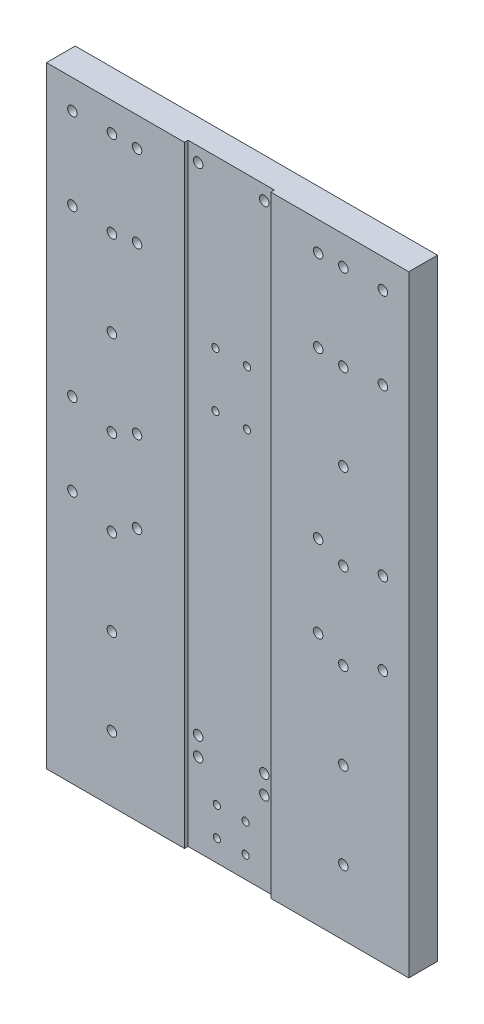
SolidWorks part; units mm, degrees
ref_plane "Piano frontale" through (0, 0, 0) normal (0, 0, 1) x (1, 0, 0)
ref_plane "Piano superiore" through (0, 0, 0) normal (0, 1, 0) x (1, 0, 0)
ref_plane "Piano destro" through (0, 0, 0) normal (1, 0, 0) x (0, 0, -1)
sketch "Schizzo1" plane through (0, 0, 0) normal (0, 0, 1) x (1, 0, 0)
  line L1 (126, -250) -> (-126, -250)
  line L2 (126, -250) -> (126, 250)
  line L3 (126, 250) -> (-126, 250)
  line L4 (-126, -250) -> (-126, 250)
  line L5 (126, -250) -> (-126, 250) construction
  line L6 (126, 250) -> (-126, -250) construction
  point P0 (0, 0)
  dimension "D1" = 252
  dimension "D2" = 500
extrude "Estrusione-Estrusione1" add sketch "Schizzo1" along normal blind 20
sketch "Schizzo2" plane through (0, 0, 20) normal (0, 0, 1) x (1, 0, 0)
  line L0 (1265.2426, 21.4119) -> (-695.7574, 21.4119) construction
  line L1 (1265.2426, 13.5541) -> (-695.7574, 13.5541) construction
  line L2 (1265.2426, 53.5541) -> (-695.7574, 53.5541) construction
  line L3 (1265.2426, 61.4119) -> (-695.7574, 61.4119) construction
  line L4 (-126, 250) -> (-126, -250)
  line L5 (-126, -250) -> (126, -250)
  line L6 (126, -250) -> (126, 250)
  line L7 (126, 250) -> (-126, 250)
  line L8 (-126, 250) -> (-126, -250) construction
  line L9 (-126, -250) -> (126, -250) construction
  line L10 (126, -250) -> (126, 250) construction
  line L11 (126, 250) -> (-126, 250) construction
  line L12 (1265.2426, 21.4119) -> (-695.7574, 21.4119) construction
  line L13 (1265.2426, 13.5541) -> (-695.7574, 13.5541) construction
  line L14 (1265.2426, 53.5541) -> (-695.7574, 53.5541) construction
  line L15 (1265.2426, 61.4119) -> (-695.7574, 61.4119) construction
  line L16 (126, -45.017) -> (-126, -45.017) construction
  line L17 (126, -25.017) -> (-126, -25.017) construction
  line L18 (126, -45.017) -> (-126, -45.017) construction
  line L19 (126, -25.017) -> (-126, -25.017) construction
  line L20 (-126, -45.017) -> (-126, -25.017) construction
  line L21 (126, -35.017) -> (-126, -35.017) construction
  line L22 (-126, -45.017) -> (126, -45.017) construction
  line L23 (-126, -45.017) -> (-126, -25.017) construction
  line L24 (-126, -25.017) -> (126, -25.017) construction
  line L25 (126, -45.017) -> (126, -25.017) construction
  circle A0 centre (110, 17.483) radius 3.9289
  circle A1 centre (110, 57.483) radius 3.9289
  circle A2 centre (-110, 17.483) radius 3.9289
  circle A3 centre (-110, 57.483) radius 3.9289
  circle A4 centre (110, -35.017) radius 3.5
  circle A5 centre (-110, -35.017) radius 3.5
  circle A6 centre (55, -35.017) radius 3.5
  circle A8 centre (-55, -35.017) radius 3.5
  circle A9 centre (20, -35.017) radius 3.5
  circle A10 centre (-20, -35.017) radius 3.5
  circle A11 centre (165, -35.017) radius 3.5 [skipped]
  dimension "D2" = 16
  dimension "D3" = 7.8579
  dimension "D4" = 16
  dimension "D5" = 7.8579
  dimension "D6" = 7
  dimension "D7" = 7
  dimension "D8" = 2
  dimension "D1" = 0
  dimension "D9" = 2
  dimension "D10" = 2
  dimension "D11" = 2
sketch "Schizzo3" plane through (0, 250, 0) normal (0, 1, 0) x (1, 0, 0)
  line L0 (126, -20) -> (-126, -20) construction
  line L1 (30, -17.5) -> (-30, -17.5)
  line L2 (30, -17.5) -> (30, -20)
  line L3 (30, -20) -> (-30, -20)
  line L4 (-30, -17.5) -> (-30, -20)
  line L5 (126, -20) -> (126, 0) construction
  line L6 (-126, -20) -> (-126, 0) construction
  line L7 (126, -20) -> (-126, -20) construction
  dimension "D1" = 2.5
  dimension "D2" = 96
  dimension "D3" = 96
extrude "Taglio-Estrusione1" cut sketch "Schizzo3" against normal through all
sketch "Schizzo4" plane through (0, 0, 17.5) normal (0, 0, 1) x (1, 0, 0)
  line L0 (30, -250) -> (30, 250) construction
  line L2 (30, 250) -> (-30, 250) construction
  line L3 (30, -250) -> (30, 250) construction
  line L6 (-30, 250) -> (-126, 250) construction
  line L7 (-30, -250) -> (-30, 250) construction
  point P11 (23, -118)
  point P14 (-23, -118)
  point P15 (-23, -105)
  point P16 (23, -105)
  point P17 (23, 240)
  point P18 (-23, 240)
  dimension "D1" = 46
  dimension "D2" = 13
  dimension "D3" = 13
  dimension "D4" = 46
  dimension "D5" = 7
  dimension "D6" = 345
  dimension "D7" = 10
  dimension "D8" = 46
  dimension "D9" = 7
  dimension "D10" = 10
  dimension "D11" = 7
  dimension "D12" = 7
sketch "Schizzo5" plane through (0, 0, 20) normal (0, 0, 1) x (1, 0, 0)
  point P4 (80.5006, 170)
  point P7 (80.5006, 110)
  point P16 (80.5006, 50)
  point P17 (80.5006, -10)
  point P18 (80.5006, -70)
  point P19 (80.5006, -130)
  point P20 (80.5006, 230)
hole_wizard "M6 Clearance Hole2" positions "Sketch7" profile "Sketch8" hole size "M6" standard "ISO"
sketch "Sketch7" plane through (0, 0, 20) normal (0, 0, 1) x (1, 0, 0)
  point P0 (80.5006, -130)
  point P3 (80.5006, -70)
  point P7 (80.5006, -10)
  point P10 (80.5006, 50)
  point P13 (80.5006, 110)
  point P16 (80.5006, 170)
  point P19 (80.5006, 230)
sketch "Sketch8" plane through (80.5006, -130, 20) normal (1, 0, 0) x (0, -1, 0)
  line L0 (0, 0) -> (0, 38.5828)
  line L1 (0, 38.5828) -> (3.3, 36.6)
  line L2 (3.3, 36.6) -> (3.3, 0)
  line L5 (3.3, 0) -> (0, 0)
  line L10 (0, 38.5828) -> (-3.3, 36.6) construction
  line L11 (0, -6.35) -> (0, 107.95) construction
  dimension "Hole Dia." = 6.6
  dimension "Hole Depth" = 36.6
  dimension "Drill Angle" = 118
sketch "Schizzo6" plane through (0, 0, 20) normal (0, 0, 1) x (1, 0, 0)
  line L0 (126, -250) -> (126, 250) construction
  line L2 (126, 250) -> (30, 250) construction
  point P23 (108, 172.8083)
  point P26 (63, 172.8083)
  point P27 (63, 229.8083)
  point P28 (108, 229.8083)
  dimension "D1" = 45
  dimension "D2" = 45
  dimension "D3" = 57
  dimension "D4" = 57
  dimension "D5" = 18
  dimension "D6" = 20.1917
  dimension "D7" = 20.1917
  dimension "D8" = 18
hole_wizard "M6 Clearance Hole4" positions "Sketch14" profile "Sketch15" hole size "M6" standard "ISO"
sketch "Sketch14" plane through (0, 0, 20) normal (0, 0, 1) x (1, 0, 0)
  point P0 (108, 172.8083)
  point P3 (108, 229.8083)
  point P6 (63, 229.8083)
  point P9 (63, 172.8083)
  point P12 (63, 57.8083)
  point P14 (63, 0.8083)
  point P16 (108, 0.8083)
  point P18 (108, 57.8083)
sketch "Sketch15" plane through (108, 172.8083, 20) normal (1, 0, 0) x (0, -1, 0)
  line L0 (0, 0) -> (0, 38.5828)
  line L1 (0, 38.5828) -> (3.3, 36.6)
  line L2 (3.3, 36.6) -> (3.3, 0)
  line L5 (3.3, 0) -> (0, 0)
  line L10 (0, 38.5828) -> (-3.3, 36.6) construction
  line L11 (0, -6.35) -> (0, 107.95) construction
  dimension "Hole Dia." = 6.6
  dimension "Hole Depth" = 36.6
  dimension "Drill Angle" = 118
hole_wizard "M6 Clearance Hole3" positions "Sketch9" profile "Sketch10" hole size "M6" standard "ISO"
sketch "Sketch9" plane through (0, 0, 17.5) normal (0, 0, 1) x (1, 0, 0)
  point P0 (23, -118)
  point P3 (23, -105)
  point P6 (-23, -118)
  point P9 (-23, -105)
  point P12 (23, 240)
  point P15 (-23, 240)
sketch "Sketch10" plane through (23, -118, 17.5) normal (1, 0, 0) x (0, -1, 0)
  line L0 (0, 0) -> (0, 38.5828)
  line L1 (0, 38.5828) -> (3.3, 36.6)
  line L2 (3.3, 36.6) -> (3.3, 0)
  line L5 (3.3, 0) -> (0, 0)
  line L10 (0, 38.5828) -> (-3.3, 36.6) construction
  line L11 (0, -6.35) -> (0, 107.95) construction
  dimension "Hole Dia." = 6.6
  dimension "Hole Depth" = 36.6
  dimension "Drill Angle" = 118
sketch "Sketch11" plane through (0, 0, 17.5) normal (0, 0, 1) x (1, 0, 0)
  line L0 (0, -250) -> (0, 250) construction
  line L1 (30, -250) -> (-30, -250) construction
  line L2 (30, 250) -> (-30, 250) construction
ref_plane "Plane1" through (0, 0, 0) normal (-1, 0, 0) x (0, 0, 1)
mirror "Mirror1" about plane through (0, 0, 0) normal (-1, 0, 0) of "M6 Clearance Hole2"
mirror "Mirror2" about plane through (0, 0, 0) normal (-1, 0, 0) of "M6 Clearance Hole4"
sketch "Sketch16" plane through (0, 0, 0) normal (0, 0, -1) x (-1, 0, 0)
  line L0 (126, 250) -> (126, -250) construction
  line L1 (126, -317.9299) -> (-126, -317.9299)
  line L2 (126, -317.9299) -> (126, -175.45)
  line L3 (126, -175.45) -> (-126, -175.45)
  line L4 (-126, -317.9299) -> (-126, -175.45)
  line L5 (-126, -250) -> (-126, 250) construction
  line L9 (-12.9, -175.45) -> (25.2, -175.45) construction
extrude "Cut-Extrude1" cut sketch "Sketch16" against normal blind 28
hole_wizard "Tap Drill for M6 Tap1" positions "Sketch17" profile "Sketch18" hole size "M6" standard "ISO" end condition through all
sketch "Sketch17" plane through (0, 0, 17.5) normal (0, 0, 1) x (1, 0, 0)
  point P0 (-11, 96.3083)
  point P2 (11, 96.3083)
  point P4 (11, 134.3083)
  point P6 (-11, 134.3083)
sketch "Sketch18" plane through (-11, 96.3083, 17.5) normal (1, 0, 0) x (0, -1, 0)
  line L0 (0, 0) -> (0, 17.5)
  line L1 (0, 17.5) -> (2.5, 17.5)
  line L2 (2.5, 17.5) -> (2.5, 0)
  line L5 (2.5, 0) -> (0, 0)
  line L11 (0, -6.35) -> (0, 107.95) construction
  dimension "Thru Hole Dia." = 5
  dimension "Thru Hole Depth" = 17.5
sketch "Sketch19" plane through (0, -195.45, 0) normal (0, -1, 0) x (-1, 0, 0)
  line L0 (0, -70.7) -> (0, 68.239) construction
  line L1 (126, -10) -> (-126, -10) construction
  line L2 (126, -20) -> (126, 0) construction
  line L3 (-126, -20) -> (-126, 0) construction
  line L5 (28.2, 0) -> (-28.2, 0) construction
  point P8 (20, -10)
  point P9 (-20, -10)
  point P12 (-20, 10)
  point P13 (20, 10)
  dimension "D1" = 20
hole_wizard "Tap Drill for M6 Tap2" positions "Sketch22" profile "Sketch23" hole size "M6" standard "ISO"
sketch "Sketch22" plane through (0, -175.45, 0) normal (0, -1, 0) x (-1, 0, 0)
  point P0 (20, -10)
  point P2 (-20, -10)
sketch "Sketch23" plane through (-20, -175.45, 10) normal (1, 0, 0) x (0, 0, -1)
  line L0 (0, 0) -> (0, 31.5022)
  line L1 (0, 31.5022) -> (2.5, 30)
  line L2 (2.5, 30) -> (2.5, 0)
  line L5 (2.5, 0) -> (0, 0)
  line L10 (0, 31.5022) -> (-2.5, 30) construction
  line L11 (0, -6.35) -> (0, 107.95) construction
  dimension "Hole Dia." = 5
  dimension "Hole Depth" = 30
  dimension "Drill Angle" = 118
hole_wizard "Tap Drill for M6 Tap3" positions "Sketch24" profile "Sketch25" hole size "M6" standard "ISO" end condition through all
sketch "Sketch24" plane through (0, 0, 0) normal (0, 0, -1) x (-1, 0, 0)
  point P0 (-10, -160.45)
  point P2 (-10, -140.45)
  point P4 (10, -140.45)
  point P6 (10, -160.45)
sketch "Sketch25" plane through (10, -160.45, 0) normal (1, 0, 0) x (0, 1, 0)
  line L0 (0, 0) -> (0, 20)
  line L1 (0, 20) -> (2.5, 20)
  line L2 (2.5, 20) -> (2.5, 0)
  line L5 (2.5, 0) -> (0, 0)
  line L11 (0, -6.35) -> (0, 107.95) construction
  dimension "Thru Hole Dia." = 5
  dimension "Thru Hole Depth" = 20
equation "\"D3@Schizzo3\"=\"D2@Schizzo3\""
equation "\"D11@Schizzo4\"=\"D5@Schizzo4\""
